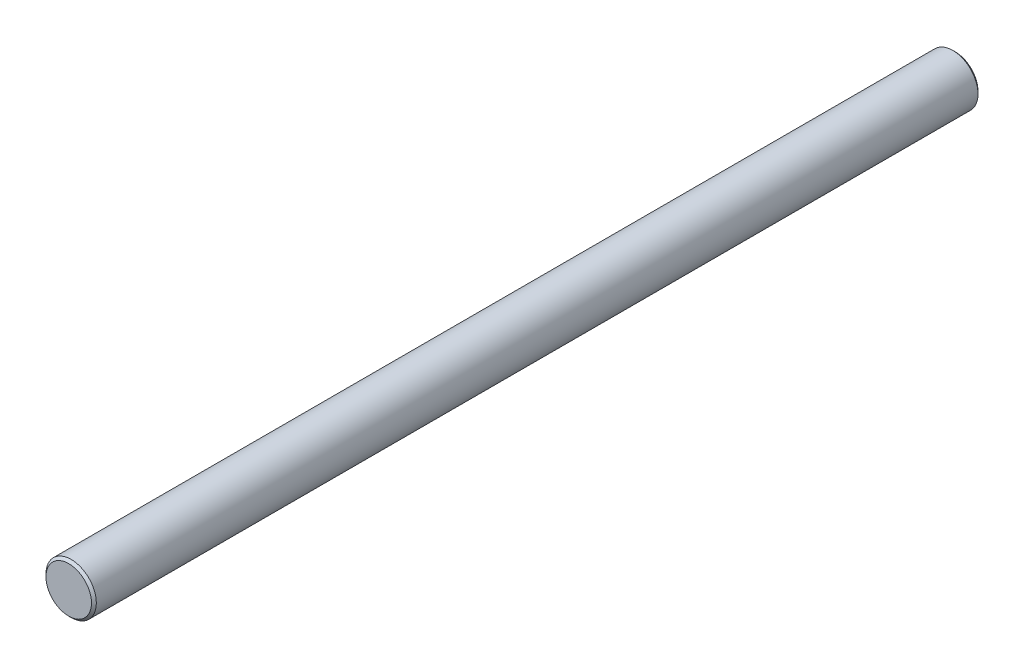
SolidWorks part; units mm, degrees
material "Alloy Steel"
ref_plane "Front Plane" through (0, 0, 0) normal (0, 0, 1) x (1, 0, 0)
ref_plane "Top Plane" through (0, 0, 0) normal (0, 1, 0) x (1, 0, 0)
ref_plane "Right Plane" through (0, 0, 0) normal (1, 0, 0) x (0, 0, -1)
sketch "Sketch1" plane through (0, 0, 0) normal (0, 0, 1) x (1, 0, 0)
  circle A0 centre (0, 0) radius 7.9375
  dimension "D1" = 15.875
extrude "Boss-Extrude1" add sketch "Sketch1" along normal mid plane 279.4
chamfer "Chamfer1" distance 0.762 angle 45 2 edges at (7.9375, 0, -139.7) (7.9375, 0, 139.7)
